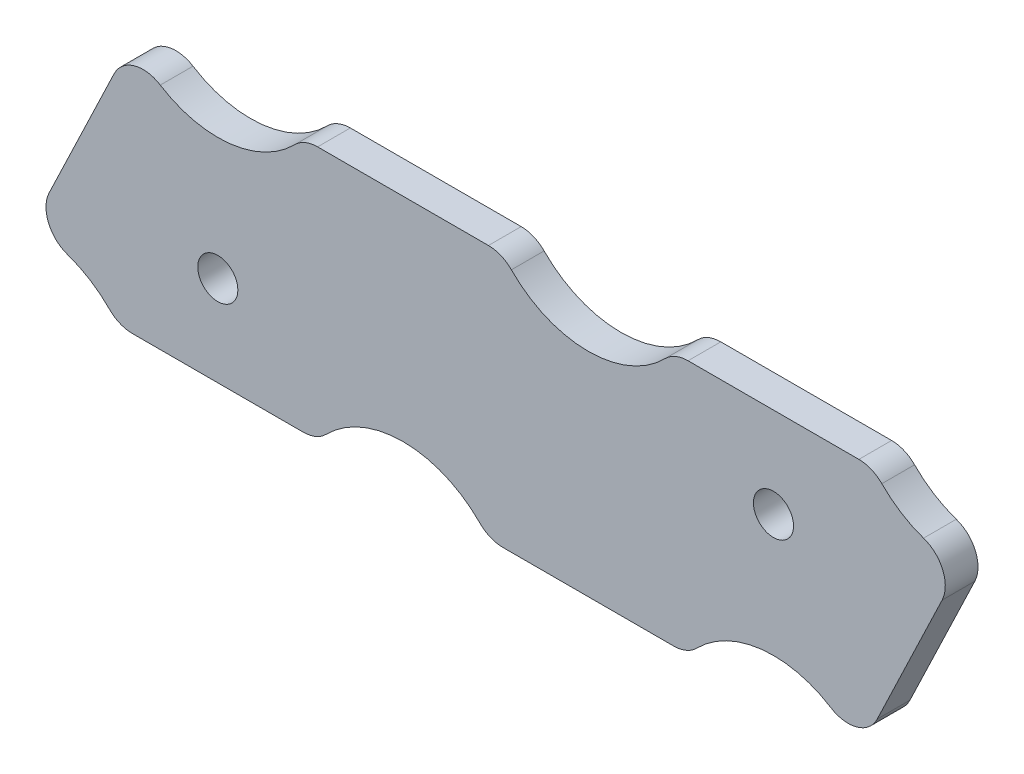
SolidWorks part; units mm, degrees
material "3003-H14"
ref_plane "X-Y Datum" through (0, 0, 0) normal (0, 0, 1) x (1, 0, 0)
ref_plane "X-Z Datum" through (0, 0, 0) normal (0, 1, 0) x (1, 0, 0)
ref_plane "Y-Z Datum" through (0, 0, 0) normal (1, 0, 0) x (0, 0, -1)
sketch "Sketch3" plane through (0, 0, 0) normal (0, 0, 1) x (1, 0, 0)
  line L0 (10.775, 10.775) -> (22.275, 34.775) construction
  line L1 (0, 0) -> (156.4633, 0) construction
  line L2 (0, 0) -> (0, 56.3098) construction
  line L3 (0, 56.3098) -> (156.4633, 56.3098) construction
  line L4 (156.4633, 0) -> (156.4633, 56.3098) construction
  line L5 (33.775, 10.775) -> (45.275, 34.775) construction
  line L6 (56.775, 10.775) -> (68.275, 34.775) construction
  line L7 (16.525, 22.775) -> (62.525, 22.775) construction
  line L8 (33.775, 10.775) -> (22.275, 34.775) construction
  line L9 (45.275, 34.775) -> (56.775, 10.775) construction
  line L10 (10.775, 10.775) -> (33.775, 10.775) construction
  line L11 (56.775, 10.775) -> (33.775, 10.775) construction
  line L12 (22.275, 34.775) -> (45.275, 34.775) construction
  line L13 (68.275, 34.775) -> (45.275, 34.775) construction
  line L14 (22.275, 34.775) -> (22.275, 10.775) construction
  line L15 (45.275, 10.775) -> (45.275, 34.775) construction
  line L16 (33.775, 10.775) -> (33.775, 34.775) construction
  line L17 (56.775, 34.775) -> (56.775, 10.775) construction
  line L18 (13.4804, 9.4786) -> (24.9804, 33.4786)
  line L19 (36.4804, 9.4786) -> (47.9804, 33.4786)
  line L20 (59.4804, 9.4786) -> (70.9804, 33.4786)
  line L21 (8.0696, 12.0714) -> (19.5696, 36.0714)
  line L22 (31.0696, 12.0714) -> (42.5696, 36.0714)
  line L23 (54.0696, 12.0714) -> (65.5696, 36.0714)
  line L24 (17.8152, 18.525) -> (57.1619, 18.525)
  line L25 (21.8881, 27.025) -> (61.2348, 27.025)
  line L26 (16.525, 27.025) -> (62.525, 27.025) construction
  line L27 (16.525, 18.525) -> (62.525, 18.525) construction
  line L28 (16.0692, 14.8813) -> (28.4808, 14.8813)
  line L29 (39.9808, 30.6687) -> (27.5692, 30.6687)
  line L48 (56.775, 10.775) -> (68.275, 10.775) construction
  line L49 (68.275, 10.775) -> (68.275, 34.775) construction
  line L50 (62.9808, 30.6687) -> (50.5692, 30.6687)
  line L51 (39.0692, 14.8813) -> (51.4808, 14.8813)
  circle A0 centre (10.775, 10.775) radius 10.775 construction
  circle A1 centre (33.775, 10.775) radius 10.775 construction
  circle A2 centre (22.275, 34.775) radius 10.775 construction
  circle A3 centre (45.275, 34.775) radius 10.775 construction
  circle A4 centre (68.275, 34.775) radius 10.775 construction
  circle A5 centre (56.775, 10.775) radius 10.775 construction
  circle A6 centre (10.775, 10.775) radius 4.7 construction
  circle A7 centre (33.775, 10.775) radius 4.7 construction
  circle A8 centre (56.775, 10.775) radius 4.7 construction
  circle A9 centre (68.275, 34.775) radius 4.7 construction
  circle A10 centre (45.275, 34.775) radius 4.7 construction
  circle A11 centre (22.275, 34.775) radius 4.7 construction
  circle A12 centre (22.275, 34.775) radius 6.7
  circle A13 centre (10.775, 10.775) radius 6.7
  circle A14 centre (33.775, 10.775) radius 6.7
  circle A15 centre (45.275, 34.775) radius 6.7
  circle A16 centre (68.275, 34.775) radius 6.7
  circle A17 centre (56.775, 10.775) radius 6.7
  circle A18 centre (125.775, 10.775) radius 10.775 construction
  circle A19 centre (102.775, 10.775) radius 10.775 construction
  circle A20 centre (79.775, 10.775) radius 10.775 construction
  circle A21 centre (91.275, 34.775) radius 10.775 construction
  circle A22 centre (114.275, 34.775) radius 10.775 construction
  circle A23 centre (137.275, 34.775) radius 10.775 construction
  dimension "D1" = 21.55
  dimension "D9" = 9.4
  dimension "D2" = 23
  dimension "D3" = 24
  dimension "D4" = 11.5
  dimension "D6" = 23
  dimension "D8" = 23
  dimension "D10" = 3
  dimension "D11" = 3
  dimension "D12" = 4.25
  dimension "D13" = 4.25
  dimension "D14" = 2
  dimension "D5" = 6
  dimension "D7" = 5
extrude "Boss-Extrude1" add sketch "Sketch3" along normal blind 2.032 contours L17 | L17 | L17 | L17 | L49 | A13 L18 A12 L21 | L25 L18 L24 L22 | L25 L22 L24 L19 | L25 L19 L24 L23 | A17 L20 A16 L23 | A14 L19 L24 L22 | A15 L22 L25 L19 | A14 L22 L24 L18 L28 | A12 L18 L25 L22 L29 | A17 L23 L24 L19 L51 | A15 L19 L25 L23 L50 region at (16.525, 22.775, 0) region at (24.1977, 16.8116, 0) region at (28.025, 22.775, 0) region at (31.8523, 28.7384, 0) region at (37.7051, 17.4114, 0) region at (39.525, 22.775, 0) region at (41.3449, 28.1386, 0) region at (47.1977, 16.8116, 0) region at (51.025, 22.775, 0) region at (54.8523, 28.7384, 0) region at (62.525, 22.775, 0)
ref_plane "Plane1" through (68.275, 0, 0) normal (1, 0, 0) x (0, 0, -1)
fillet "Fillet1" radius 2 12 edges at (62.9808, 30.6687, 1.016) (50.5692, 30.6687, 1.016) (39.9808, 30.6687, 1.016) (27.5692, 30.6687, 1.016) (16.0692, 14.8813, 1.016) (28.4808, 14.8813, 1.016) (39.0692, 14.8813, 1.016) (51.4808, 14.8813, 1.016) (68.3917, 28.076, 1.016) (62.0692, 14.8813, 1.016) (10.6583, 17.474, 1.016) (16.9808, 30.6687, 1.016)
sketch "Sketch4" plane through (0, 0, 2.032) normal (0, 0, 1) x (1, 0, 0)
  circle A0 centre (22.275, 20.4921) radius 1.2446
  circle A1 centre (56.775, 25.0579) radius 1.2446
  point P0 (56.775, 25.0579)
  point P1 (22.275, 20.4921)
  dimension "D1" = 2.4892
extrude "Cut-Extrude1" cut sketch "Sketch4" against normal through all
sketch "Sketch5" [suppressed] plane through (0, 0, 2.032) normal (0, 0, 1) x (1, 0, 0)
  line L0 (13.8196, 24.0714) -> (66.4728, 24.0714)
  line L1 (11.8041, 19.8652) -> (15.835, 28.2776) construction
  line L2 (63.215, 17.2724) -> (67.2459, 25.6848) construction
  line L3 (65.2304, 21.4786) -> (12.5772, 21.4786)
  line L5 (40.1462, 24.0714) -> (40.1462, 21.4786)
  line L6 (38.9038, 21.4786) -> (38.9038, 24.0714)
  line L7 (38.9038, 22.775) -> (40.1462, 22.775)
  line L9 (16.025, 27.275) -> (63.025, 27.275)
  line L10 (16.025, 27.275) -> (16.025, 18.275)
  line L11 (16.025, 18.275) -> (63.025, 18.275)
  line L12 (63.025, 27.275) -> (63.025, 18.275)
  line L13 (16.025, 27.275) -> (63.025, 18.275) construction
  line L14 (16.025, 18.275) -> (63.025, 27.275) construction
  point P11 (40.1462, 24.0714)
  point P15 (39.525, 22.775)
  dimension "D1" = 47
  dimension "D2" = 9
